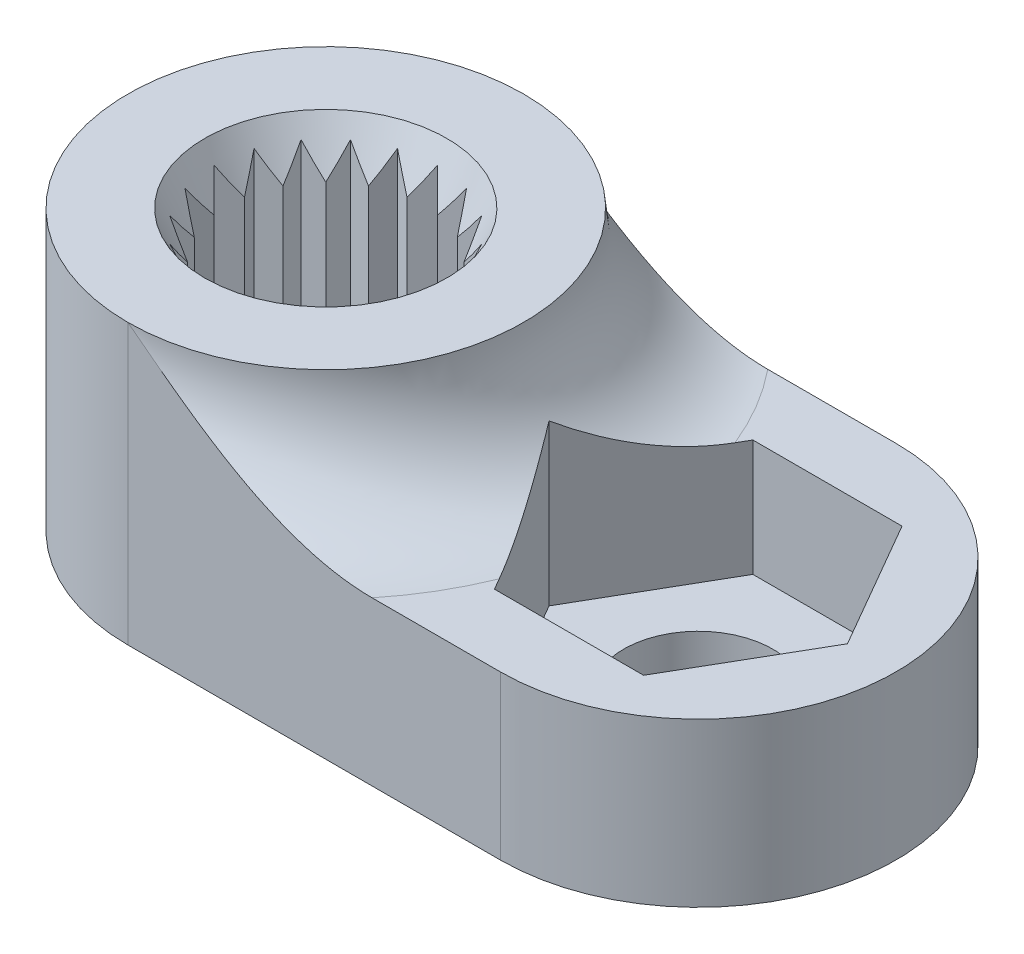
SolidWorks part; units mm, degrees
ref_plane "Front Plane" through (0, 0, 0) normal (0, 0, 1) x (1, 0, 0)
ref_plane "Top Plane" through (0, 0, 0) normal (0, 1, 0) x (1, 0, 0)
ref_plane "Right Plane" through (0, 0, 0) normal (1, 0, 0) x (0, 0, -1)
sketch "Sketch1" plane through (0, 0, 0) normal (0, 1, 0) x (1, 0, 0)
  line L0 (-4, 0) -> (4, 0) construction
  line L1 (-4, 4.25) -> (4, 4.25)
  line L2 (-4, -4.25) -> (4, -4.25)
  arc A0 (-4, 4.25) -> (-4, -4.25) centre (-4, 0) ccw
  arc A1 (4, -4.25) -> (4, 4.25) centre (4, 0) ccw
  point P2 (0, 0)
  dimension "D1" = 8
  dimension "D2" = 8.5
extrude "Boss-Extrude1" add sketch "Sketch1" along normal blind 6
sketch "Sketch2" plane through (0, 6, 0) normal (0, 1, 0) x (1, 0, 0)
  circle A0 centre (-4, 0) radius 2.1
  arc A1 (-4, 4.25) -> (-4, -4.25) centre (-4, 0) ccw construction
  dimension "D1" = 4.2
extrude "Cut-Extrude1" cut sketch "Sketch2" against normal blind 3.5
sketch "Sketch3" plane through (0, 0, 0) normal (0, -1, 0) x (1, 0, 0)
  circle A0 centre (-4, 0) radius 2.5
  arc A1 (-4, 4.25) -> (-4, -4.25) centre (-4, 0) ccw construction
  dimension "D1" = 5
extrude "Cut-Extrude2" cut sketch "Sketch3" against normal blind 1.5
sketch "Sketch4" plane through (0, 2.5, 0) normal (0, 1, 0) x (1, 0, 0)
  circle A0 centre (-4, 0) radius 1.35
  dimension "D1" = 2.7
extrude "Cut-Extrude3" cut sketch "Sketch4" against normal through all
sketch "Sketch5" plane through (0, 6, 0) normal (0, 1, 0) x (1, 0, 0)
  line L1 (7.2043, 0) -> (5.6021, 2.775)
  line L2 (5.6021, 2.775) -> (2.3979, 2.775)
  line L3 (2.3979, 2.775) -> (0.7957, 0)
  line L4 (0.7957, 0) -> (2.3979, -2.775)
  line L5 (2.3979, -2.775) -> (5.6021, -2.775)
  line L6 (5.6021, -2.775) -> (7.2043, 0)
  circle A0 centre (4, 0) radius 2.775 construction
  arc A1 (4, -4.25) -> (4, 4.25) centre (4, 0) ccw construction
  dimension "D1" = 5.55
extrude "Cut-Extrude4" cut sketch "Sketch5" against normal blind 5
sketch "Sketch6" plane through (0, 1, 0) normal (0, 1, 0) x (1, 0, 0)
  circle A0 centre (4, 0) radius 1.6
  arc A1 (4, -4.25) -> (4, 4.25) centre (4, 0) ccw construction
  dimension "D1" = 3.2
extrude "Cut-Extrude5" cut sketch "Sketch6" against normal through all
chamfer "Chamfer2" distance 0.5 distance2 1 1 edges at (-4, 6, 2.1) first distance on face at (4, 6, 0)
sketch "Sketch8" plane through (0, 6, 0) normal (0, 1, 0) x (1, 0, 0)
  line L0 (4, 4.25) -> (-4, 4.25) construction
  line L1 (-4, -4.25) -> (4, -4.25) construction
  line L2 (4, 4.25) -> (-4, 4.25)
  line L3 (-4, -4.25) -> (4, -4.25)
  arc A0 (4, -4.25) -> (4, 4.25) centre (4, 0) ccw construction
  arc A1 (4, -4.25) -> (4, 4.25) centre (4, 0) ccw
  arc A2 (-4, 4.25) -> (-4, -4.25) centre (-4, 0) cw
  arc A3 (-4, 4.25) -> (-4, -4.25) centre (-4, 0) ccw construction
extrude "Cut-Extrude6" cut sketch "Sketch8" against normal blind 2.5
fillet "Fillet1" radius 2.5 1 edges at (0.25, 3.5, 0)
sketch "Sketch9" plane through (0, 6, 0) normal (0, 1, 0) x (1, 0, 0)
  line L0 (-4, 0) -> (-1.6, 0) construction
  line L1 (-1.6, 0) -> (-1.9259, 0.3285)
  line L2 (-1.9259, 0.3285) -> (-1.9259, -0.3285) construction
  line L3 (-1.9259, -0.3285) -> (-1.6, 0)
  line L4 (-1.9259, 0.3285) -> (-4, 0)
  line L5 (-4, 0) -> (-1.9259, -0.3285)
  circle A1 centre (-4, 0) radius 1.35 construction
  circle A2 centre (-4, 0) radius 1.35 construction
  point P6 (-1.9259, 0)
  dimension "D1" = 18
  dimension "D2" = 2.1
  dimension "D3" = 2.4
ref_axis "Axis1" through (-4, 2.5, 0) along (0, 1, 0)
extrude "Cut-Extrude7" cut sketch "Sketch9" against normal up to surface (3.5 mm away) up to face at (-4, 2.5, 1.35)
pattern_circular "CirPattern1" count 20 over 360 about axis through (-4, 2.5, 0) along (0, 1, 0) of "Cut-Extrude7"
